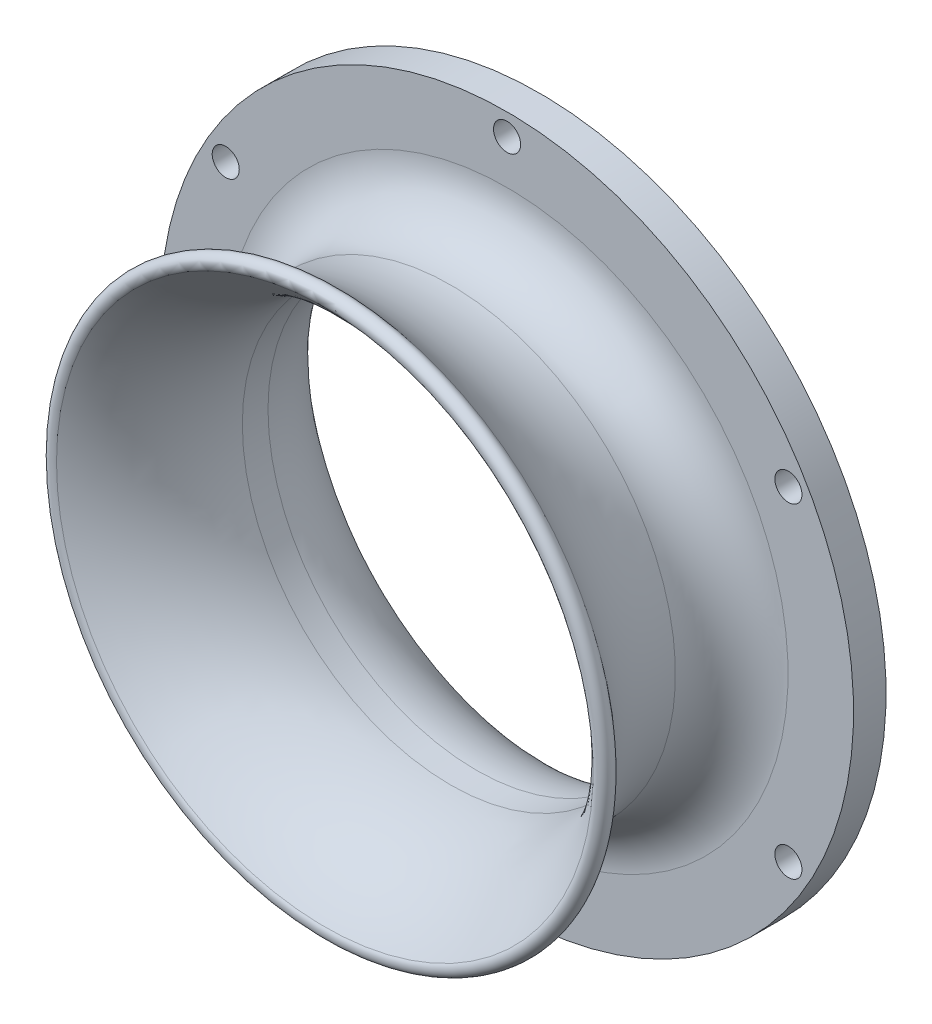
SolidWorks part; units mm, degrees
material "Nylon 6/10"
ref_plane "Front Plane" through (0, 0, 0) normal (0, 0, 1) x (1, 0, 0)
ref_plane "Top Plane" through (0, 0, 0) normal (0, 1, 0) x (1, 0, 0)
ref_plane "Right Plane" through (0, 0, 0) normal (1, 0, 0) x (0, 0, -1)
sketch "Sketch1" plane through (0, 0, 0) normal (1, 0, 0) x (0, 0, -1)
  line L0 (0, 0) -> (-49.6085, 0) construction
  line L1 (2.3704, 19.25) -> (0, 19.25)
  line L2 (0, 52.938) -> (0, 0) construction
  line L3 (11.2, 27.5) -> (8.2, 27.5)
  line L4 (8.2, 27.5) -> (8.2, 32)
  line L5 (8.2, 32) -> (5.2, 32)
  line L6 (5.2, 32) -> (5.2, 25.95)
  arc A0 (2.3704, 19.25) -> (11.2, 27.5) centre (2.3704, 28.1) ccw
  arc A1 (0, 19.25) -> (-11.6316, 24.7787) centre (0, 34.25) cw
  arc A2 (5.2, 25.95) -> (0, 20.75) centre (0, 25.95) cw
  arc A3 (0, 20.75) -> (-10.4684, 25.7258) centre (0, 34.25) cw
  arc A4 (-10.4684, 25.7258) -> (-11.6316, 24.7787) centre (-11.05, 25.2522) ccw
  dimension "D2" = 8.85
  dimension "D6" = 5.2
  dimension "D7" = 20
  dimension "D8" = 15
  dimension "D9" = 13.5
  dimension "D10" = 0.75
  dimension "D1" = 38.5
  dimension "D3" = 3
  dimension "D4" = 3
  dimension "D5" = 8.2
  dimension "D11" = 55
  dimension "D12" = 64
revolve "Revolve1" add sketch "Sketch1" angle 360 about L0
hole_wizard "Ø2.5 (2.5) Diameter Hole1" positions "Sketch3" profile "Sketch2" hole size "Ø2.5" standard "Ansi Metric"
sketch "Sketch3" plane through (0, 0, -5.2) normal (0, 0, 1) x (1, 0, 0)
  point P0 (0, 30)
  dimension "D1" = 30
sketch "Sketch2" plane through (0, 30, -5.2) normal (1, 0, 0) x (0, -1, 0)
  line L0 (0, 0) -> (0, 23.7511)
  line L1 (0, 23.7511) -> (1.25, 23)
  line L2 (1.25, 23) -> (1.25, 0)
  line L5 (1.25, 0) -> (0, 0)
  line L10 (0, 23.7511) -> (-1.25, 23) construction
  line L11 (0, -6.35) -> (0, 107.95) construction
  dimension "Hole Dia." = 2.5
  dimension "Hole Depth" = 23
  dimension "Drill Angle" = 118
ref_axis "Axis1" through (0, 0, 12.95) along (0, 0, -1)
pattern_circular "CirPattern1" count 6 over 360 about axis through (0, 0, 12.95) along (0, 0, -1) of "Ø2.5 (2.5) Diameter Hole1"
